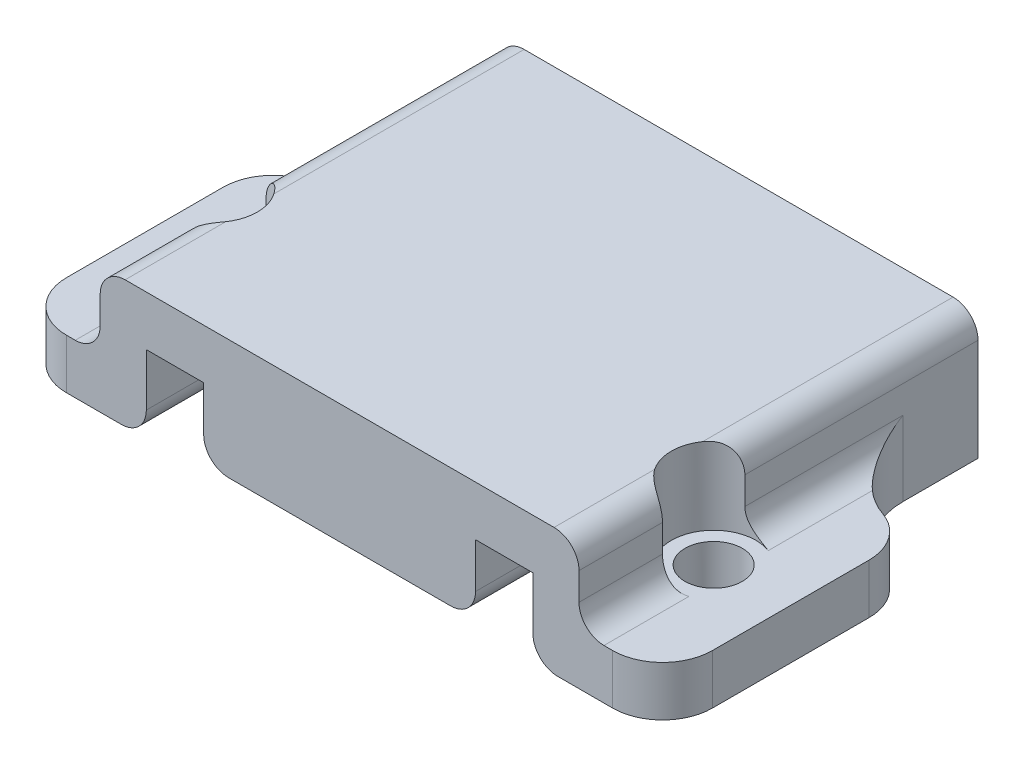
SolidWorks part; units mm, degrees
ref_plane "Front Plane" through (0, 0, 0) normal (0, 0, 1) x (1, 0, 0)
ref_plane "Top Plane" through (0, 0, 0) normal (0, 1, 0) x (1, 0, 0)
ref_plane "Right Plane" through (0, 0, 0) normal (1, 0, 0) x (0, 0, -1)
sketch "Sketch1" plane through (0, 0, 0) normal (0, 1, 0) x (1, 0, 0)
  line L4 (7.6, 15) -> (5.6, 15)
  line L5 (7.6, -5) -> (7.6, 15)
  line L6 (5.6, -5) -> (7.6, -5)
  line L7 (5.6, 15) -> (5.6, -5)
  line L8 (7.6, 15) -> (5.6, 15)
  line L9 (7.6, -5) -> (7.6, 15)
  line L10 (5.6, -5) -> (7.6, -5)
  line L11 (5.6, 15) -> (5.6, -5)
  line L12 (-5.6, 15) -> (-7.6, 15)
  line L13 (-5.6, -5) -> (-5.6, 15)
  line L14 (-7.6, -5) -> (-5.6, -5)
  line L15 (-7.6, 15) -> (-7.6, -5)
  line L16 (-5.6, 15) -> (-7.6, 15)
  line L17 (-5.6, -5) -> (-5.6, 15)
  line L18 (-7.6, -5) -> (-5.6, -5)
  line L19 (-7.6, 15) -> (-7.6, -5)
  circle A1 centre (-10, 0) radius 0.95
  circle A2 centre (-10, 0) radius 0.95
  circle A3 centre (10, 0) radius 0.95
  circle A4 centre (10, 0) radius 0.95
  dimension "D1" = 0
  dimension "D2" = 0
  dimension "D3" = 0
  dimension "D4" = 0
ref_plane "Plane1" through (0, -3.1, 0) normal (0, 1, 0) x (1, 0, 0)
sketch "Sketch2" plane through (0, 0, 0) normal (0, 1, 0) x (1, 0, 0)
  line L0 (-7.6, -5) -> (-5.6, -5) construction
  line L1 (9.6, -5) -> (-9.6, -5)
  line L2 (9.6, -5) -> (9.6, 5)
  line L3 (9.6, 5) -> (-9.6, 5) construction
  line L4 (-9.6, -5) -> (-9.6, 5)
  line L5 (-9.6, 5) -> (-9.6, 11)
  line L6 (-9.6, 11) -> (9.6, 11)
  line L7 (9.6, 11) -> (9.6, 5)
  line L8 (7.6, -5) -> (7.6, 15) construction
  point P7 (0, -5)
  dimension "D1" = 10
  dimension "D2" = 16
  dimension "D3" = 2
extrude "Boss-Extrude1" add sketch "Sketch2" along normal blind 2
sketch "Sketch3" plane through (0, 0, 0) normal (0, 1, 0) x (1, 0, 0)
  line L0 (9.6, 11) -> (-9.6, 11) construction
  line L1 (-9.6, -5) -> (-7.75, -5)
  line L2 (-9.6, -5) -> (-9.6, 11)
  line L3 (-9.6, 11) -> (-7.75, 11)
  line L4 (-7.75, -5) -> (-7.75, 11)
  line L5 (9.6, -5) -> (7.75, -5)
  line L6 (9.6, -5) -> (9.6, 11)
  line L7 (9.6, 11) -> (7.75, 11)
  line L8 (7.75, -5) -> (7.75, 11)
  line L11 (-7.6, 15) -> (-7.6, -5) construction
  line L12 (7.6, -5) -> (7.6, 15) construction
  point P12 (-8.023, 11)
  point P13 (7.93, 11)
  dimension "D1" = 0.15
  dimension "D2" = 0.15
extrude "Boss-Extrude2" add sketch "Sketch3" against normal up to surface (3.1 mm away) up to plane "Plane1"
sketch "Sketch4" plane through (0, -3.1, 0) normal (0, 1, 0) x (1, 0, 0)
  line L0 (-9.6, -5) -> (-9.6, 5) construction
  line L1 (9.6, -5) -> (9.6, 5) construction
  line L2 (-9.6, -5) -> (-9.6, 5)
  line L3 (9.6, -5) -> (9.6, 5)
  line L4 (9.6, 5) -> (12.95, 5)
  line L5 (12.95, 5) -> (12.95, -5)
  line L6 (12.95, -5) -> (9.6, -5)
  line L7 (-9.6, 5) -> (-12.95, 5)
  line L8 (-12.95, 5) -> (-12.95, -5)
  line L9 (-12.95, -5) -> (-9.6, -5)
  circle A0 centre (10, 0) radius 0.95 construction
  circle A1 centre (-10, 0) radius 0.95 construction
  circle A2 centre (10, 0) radius 0.95 construction
  circle A3 centre (-10, 0) radius 0.95 construction
  circle A4 centre (10, 0) radius 1.15 construction
  circle A5 centre (-10, 0) radius 1.15 construction
  point P12 (10.95, 0)
  dimension "D1" = 2
  dimension "D2" = 0.2
extrude "Boss-Extrude3" add sketch "Sketch4" along normal blind 2
sketch "Sketch5" plane through (0, 0, 0) normal (0, -1, 0) x (1, 0, 0)
  line L1 (-5.45, 5) -> (5.45, 5)
  line L2 (-5.45, 5) -> (-5.45, 2)
  line L3 (-5.45, 2) -> (5.45, 2)
  line L4 (5.45, 5) -> (5.45, 2)
  line L7 (-5.6, 5) -> (-5.6, -15) construction
  line L8 (-7.75, 5) -> (7.75, 5) construction
  point P7 (0, 2)
  dimension "D1" = 3
  dimension "D2" = 0.15
extrude "Boss-Extrude4" add sketch "Sketch5" along normal blind 2.8
fillet "Fillet2" radius 1 8 edges at (7.75, -3.1, -3) (-7.75, -3.1, -3) (-9.6, -1.1, 0) (9.6, -1.1, 0) (5.45, -2.8, 3.5) (-5.45, -2.8, 3.5) (-9.6, 2, -3) (9.6, 2, -3)
sketch "Sketch7" plane through (0, 2, 0) normal (0, 1, 0) x (1, 0, 0)
  circle A0 centre (-10, 0) radius 0.95 construction
  circle A1 centre (10, 0) radius 0.95 construction
  circle A2 centre (-10, 0) radius 0.95 construction
  circle A3 centre (10, 0) radius 0.95 construction
  circle A4 centre (-10, 0) radius 1.15
  circle A5 centre (10, 0) radius 1.15
  dimension "D1" = 0.2
extrude "Cut-Extrude2" cut sketch "Sketch7" against normal through all
sketch "Sketch8" plane through (0, 2, 0) normal (0, 1, 0) x (1, 0, 0)
  circle A0 centre (-10, 0) radius 0.95 construction
  circle A1 centre (10, 0) radius 0.95 construction
  circle A2 centre (-10, 0) radius 0.95 construction
  circle A3 centre (10, 0) radius 0.95 construction
  circle A4 centre (-10, 0) radius 1.7
  circle A5 centre (10, 0) radius 1.7
  dimension "D1" = 3.4
extrude "Cut-Extrude3" cut sketch "Sketch8" against normal up to surface (3.1 mm away) up to face at (11.475, -1.1, 0)
fillet "Fillet3" radius 3 2 edges at (9.6, -1.6, -5) (-9.6, -1.6, -5)
fillet "Fillet4" radius 2 4 edges at (12.95, -2.1, -5) (12.95, -2.1, 5) (-12.95, -2.1, -5) (-12.95, -2.1, 5)
